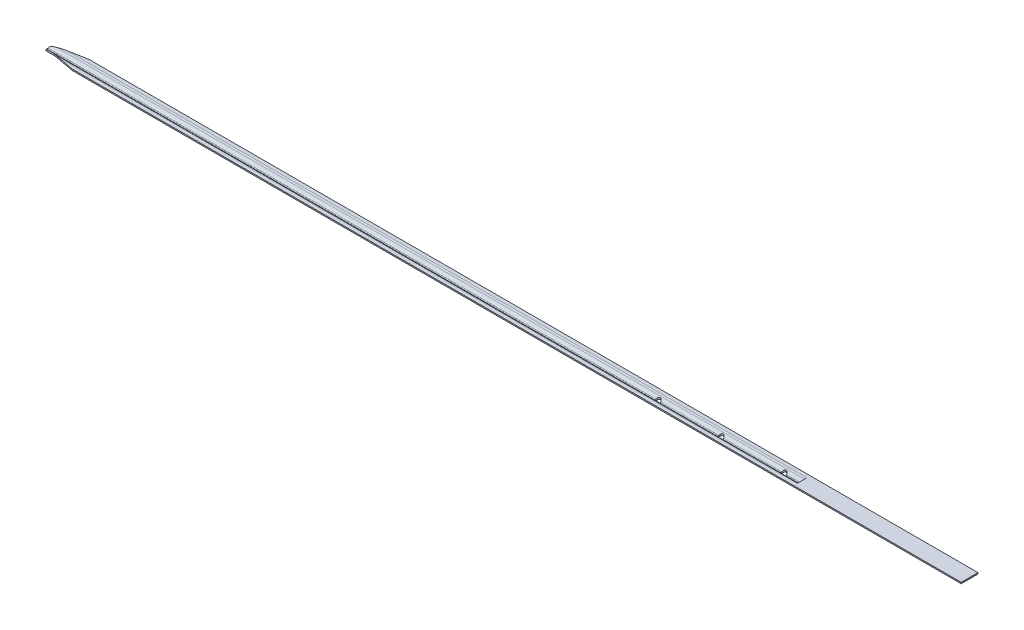
SolidWorks part; units mm, degrees
ref_plane "Спереди" through (0, 0, 0) normal (0, 0, 1) x (1, 0, 0)
ref_plane "Сверху" through (0, 0, 0) normal (0, 1, 0) x (1, 0, 0)
ref_plane "Справа" through (0, 0, 0) normal (1, 0, 0) x (0, 0, -1)
sketch "Эскиз1" plane through (0, 0, 0) normal (1, 0, 0) x (0, 0, -1)
  line L0 (-10, 0) -> (-5, 0)
  line L1 (-5, 0) -> (0, -5)
  line L2 (0, -5) -> (5, 0)
  line L3 (5, 0) -> (10, 0)
  line L4 (0, -5) -> (0, 0) construction
  line L5 (-12.4733, -2.5) -> (12.4733, -2.5) construction
  point P12 (0, -2.5)
  dimension "D1" = 5
  dimension "D3" = 90
sketch "Эскиз5" plane through (0, 0, 0) normal (1, 0, 0) x (0, 0, -1)
  line L0 (-10, 0) -> (-5, 0) construction
  line L1 (-5, 0) -> (0, -5) construction
  line L2 (0, -5) -> (5, 0) construction
  line L3 (5, 0) -> (10, 0) construction
  line L4 (-10, 0) -> (-5.8284, 0) construction
  line L5 (-4.4142, -0.5858) -> (-1.4142, -3.5858) construction
  line L6 (1.4142, -3.5858) -> (4.4142, -0.5858) construction
  line L7 (5.8284, 0) -> (10, 0) construction
  line L8 (-10, -0.75) -> (-5.8284, -0.75)
  line L9 (-4.9445, -1.1161) -> (-1.9445, -4.1161)
  line L10 (1.9445, -4.1161) -> (4.9445, -1.1161)
  line L11 (5.8284, -0.75) -> (10, -0.75)
  line L12 (-10, 0.75) -> (-5.8284, 0.75)
  line L13 (-3.8839, -0.0555) -> (-0.8839, -3.0555)
  line L14 (0.8839, -3.0555) -> (3.8839, -0.0555)
  line L15 (5.8284, 0.75) -> (10, 0.75)
  line L16 (-10, -0.75) -> (-10, 0.75)
  line L17 (10, -0.75) -> (10, 0.75)
  arc A0 (-5.8284, 0) -> (-4.4142, -0.5858) centre (-5.8284, -2) cw construction
  arc A1 (-1.4142, -3.5858) -> (1.4142, -3.5858) centre (0, -2.1716) ccw construction
  arc A2 (4.4142, -0.5858) -> (5.8284, 0) centre (5.8284, -2) cw construction
  arc A3 (-5.8284, -0.75) -> (-4.9445, -1.1161) centre (-5.8284, -2) cw
  arc A4 (-1.9445, -4.1161) -> (1.9445, -4.1161) centre (0, -2.1716) ccw
  arc A5 (4.9445, -1.1161) -> (5.8284, -0.75) centre (5.8284, -2) cw
  arc A6 (-5.8284, 0.75) -> (-3.8839, -0.0555) centre (-5.8284, -2) cw
  arc A7 (-0.8839, -3.0555) -> (0.8839, -3.0555) centre (0, -2.1716) ccw
  arc A8 (3.8839, -0.0555) -> (5.8284, 0.75) centre (5.8284, -2) cw
  dimension "D1" = 2
  dimension "D2" = 0.75
  dimension "D3" = 0.75
extrude "Бобышка-Вытянуть1" add sketch "Эскиз5" against normal blind 900
sketch "Эскиз6" plane through (0, 0, 0) normal (1, 0, 0) x (0, 0, -1)
  line L1 (10, 0.75) -> (-10, 0.75)
  line L2 (10, 0.75) -> (10, -0.75)
  line L3 (10, -0.75) -> (-10, -0.75)
  line L4 (-10, 0.75) -> (-10, -0.75)
extrude "Бобышка-Вытянуть2" add sketch "Эскиз6" along normal blind 200
sketch "Эскиз2" plane through (0, 0, 0) normal (0, 1, 0) x (1, 0, 0)
  line L0 (0, 0) -> (-900, 0) construction
  line L1 (-900, -5.8284) -> (-900, -10) construction
  line L2 (-897.5536, 2.9485) -> (-860, 10)
  line L3 (-897.5536, -2.9485) -> (-860, -10)
  line L4 (200, 10) -> (-900, 10) construction
  arc A0 (-897.5536, 2.9485) -> (-897.5536, -2.9485) centre (-897, 0) ccw
  point P7 (0, 0)
  point P9 (0, 0)
  point P13 (0, 0)
  point P15 (0, 0)
  point P16 (0, 0)
  point P18 (0, 0)
  point P19 (0, 0)
  dimension "D1" = 3
  dimension "D2" = 40
extrude "Вырез-Вытянуть1" cut sketch "Эскиз2" against normal through all and the other way through all
sketch "Эскиз3" plane through (0, 0, 0) normal (0, 1, 0) x (1, 0, 0)
  circle A1 centre (-22, 0) radius 3
  circle A2 centre (-22, 0) radius 3
  circle A3 centre (-172, 0) radius 3
  circle A4 centre (-172, 0) radius 3
  circle A5 centre (-97, 0) radius 3
  circle A6 centre (-97, 0) radius 3
  dimension "D1" = 0
  dimension "D2" = 0
  dimension "D3" = 0
extrude "Вырез-Вытянуть2" cut sketch "Эскиз3" against normal through all and the other way through all
ref_plane "Плоскость1" through (0, 0, 0) normal (0, 1, 0) x (1, 0, 0)
equation "\"D1@Эскиз5\"=\"радиус сгиба\""
equation "\"D3@Эскиз5\"=\"D2@Эскиз5\""
equation "\"длина лезвия\"=900"
equation "\"радиус острия\"=3"
equation "\"длина острия\"=40"
equation "\"ширина лезвия\"=20"
equation "\"радиус сгиба\"=2"
equation "\"высота ребра жесткости\"=7"
equation "\"тощина\"=1.5"
equation "\"длина рукоятки\"=200"
equation "\"тлщина рукоятки\"=30"
equation "\"диаметр заклепки\"=6"
equation "\"расстояние между заклнпками\"=75"
equation "\"глубина заклепки\"=6"
equation "\"отступ от заклепки\"=3"
equation "\"диаметр шляпы\"=\"диаметр заклепки\" + 2*\"отступ от заклепки\""
equation "\"радиус скруглений\"=5"
equation "\"высота головки\"=1.2"
equation "\"высота купола\"=3"
equation "\"D2@Эскиз5\"=\"тощина\" / 2"
equation "\"D2@Эскиз1\"=\"ширина лезвия\""
equation "\"D1@Эскиз1\"=25.00мм/5"
equation "\"D1@Бобышка-Вытянуть1\"=\"длина лезвия\""
equation "\"D2@Бобышка-Вытянуть1\"=\"длина рукоятки\""
equation "\"D1@Эскиз2\"=\"радиус острия\""
equation "\"D2@Эскиз2\"=\"длина острия\""
equation "\"D1@Бобышка-Вытянуть2\"=\"длина рукоятки\""
